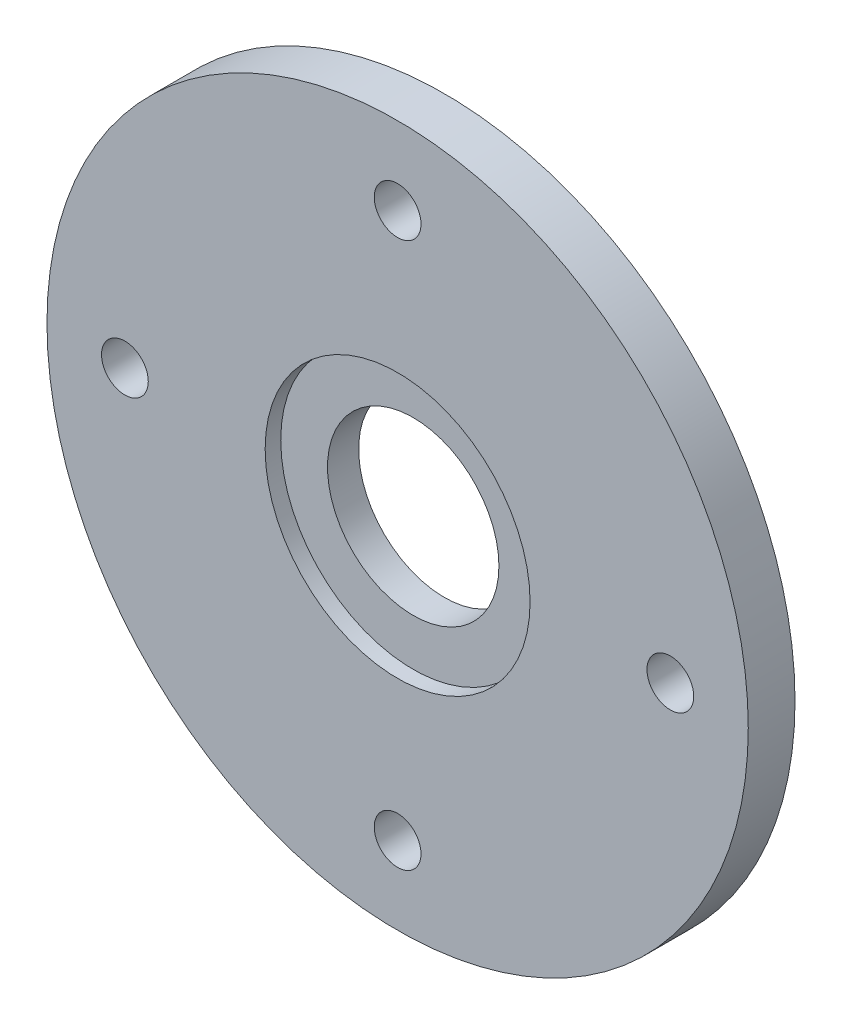
SolidWorks part; units mm, degrees
ref_plane "正面" through (0, 0, 0) normal (0, 0, 1) x (1, 0, 0)
ref_plane "平面" through (0, 0, 0) normal (0, 1, 0) x (1, 0, 0)
ref_plane "右側面" through (0, 0, 0) normal (1, 0, 0) x (0, 0, -1)
sketch "ｽｹｯﾁ1" plane through (0, 0, 0) normal (0, 0, 1) x (1, 0, 0)
  line L0 (0, 0) -> (-17.5, 0) construction
  circle A0 centre (0, 0) radius 5.5
  circle A1 centre (-17.5, 0) radius 1.5 construction
  circle A2 centre (0, 0) radius 22.5
  dimension "D1" = 17.5
  dimension "D2" = 11
  dimension "D3" = 3
  dimension "D4" = 45
extrude "ﾎﾞｽ - 押し出し1" add sketch "ｽｹｯﾁ1" along normal blind 3
sketch "ｽｹｯﾁ2" plane through (0, 0, 3) normal (0, 0, 1) x (1, 0, 0)
  circle A0 centre (-17.5, 0) radius 1.5
  circle A1 centre (-17.5, 0) radius 1.5 construction
extrude "ｶｯﾄ - 押し出し1" cut sketch "ｽｹｯﾁ2" against normal through all
pattern_circular "円形ﾊﾟﾀｰﾝ2" count 4 over 360 about axis through (0, 0, 3) along (0, 0, -1) of "ｶｯﾄ - 押し出し1"
sketch "ｽｹｯﾁ3" plane through (0, 0, 3) normal (0, 0, 1) x (1, 0, 0)
  circle A0 centre (0, 0) radius 8.5
  circle A1 centre (0, 0) radius 5.5
  circle A2 centre (0, 0) radius 5.5 construction
  dimension "D1" = 17
extrude "ｶｯﾄ - 押し出し2" cut sketch "ｽｹｯﾁ3" against normal blind 1
